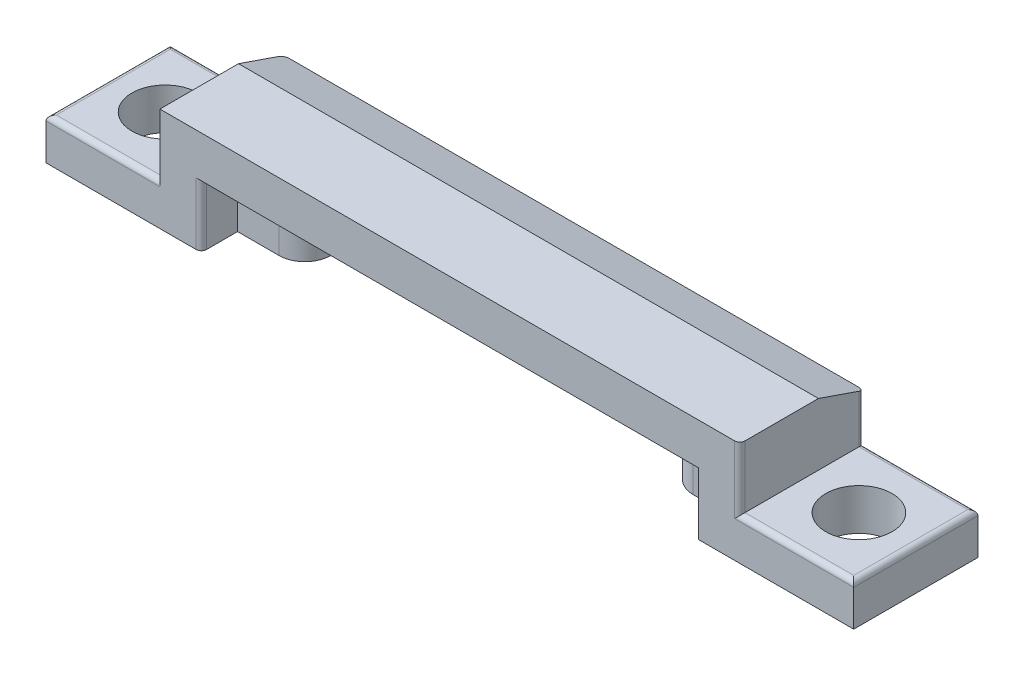
SolidWorks part; units mm, degrees
ref_plane "Ebene vorne" through (0, 0, 0) normal (0, 0, 1) x (1, 0, 0)
ref_plane "Ebene oben" through (0, 0, 0) normal (0, 1, 0) x (1, 0, 0)
ref_plane "Ebene rechts" through (0, 0, 0) normal (1, 0, 0) x (0, 0, -1)
sketch "Skizze1" plane through (0, 0, 0) normal (0, 0, 1) x (1, 0, 0)
  line L0 (0, 0) -> (7.5, 0)
  line L1 (7.5, 0) -> (7.5, 3)
  line L2 (7.5, 3) -> (31.5, 3)
  line L3 (31.5, 3) -> (31.5, 0)
  line L4 (31.5, 0) -> (39, 0)
  line L5 (39, 0) -> (39, 2)
  line L8 (33.5, 5) -> (5.5, 5)
  line L11 (0, 2) -> (0, 0)
  line L12 (33.5, 5) -> (33.5, 2)
  line L13 (-9, 2) -> (48, 2) construction
  line L14 (33.5, 2) -> (39, 2)
  line L15 (5.5, 5) -> (5.5, 2)
  line L16 (-9, 2) -> (48, 2) construction
  line L17 (5.5, 2) -> (0, 2)
  dimension "D1" = 24
  dimension "D2" = 3
  dimension "D3" = 7.5
  dimension "D4" = 7.5
  dimension "D5" = 5
  dimension "D9" = 2
  dimension "D10" = 2
extrude "Aufsatz-Linear austragen1" add sketch "Skizze1" along normal blind 6
sketch "Skizze4" plane through (0, 0, 0) normal (0, -1, 0) x (1, 0, 0)
  line L0 (39, 6) -> (39, 0) construction
  line L1 (31.5, 0) -> (39, 0) construction
  circle A0 centre (36.25, 3) radius 1.6
  dimension "D1" = 3.2
  dimension "D3" = 3
  dimension "D2" = 2.75
extrude "Schnitt-Linear austragen1" cut sketch "Skizze4" against normal blind 3
ref_plane "Ebene1" through (0, 5, 0) normal (0, -1, 0) x (-1, 0, 0)
ref_plane "Ebene2" through (19.5, 0, 0) normal (-1, 0, 0) x (0, 0, 1)
ref_plane "Ebene4" through (0, 0, 3) normal (0, 0, 1) x (1, 0, 0)
sketch "Skizze12" plane through (0, 3, 0) normal (0, -1, 0) x (1, 0, 0)
  line L0 (31.5, 1.75) -> (29.5, 1.75)
  line L1 (31.5, 6) -> (31.5, 0) construction
  line L2 (2.75, 3) -> (-2.75, 3) construction
  line L3 (29.5, 4.25) -> (31.5, 4.25)
  line L4 (31.5, 6) -> (31.5, 0) construction
  line L5 (31.5, 4.25) -> (31.5, 1.75)
  arc A0 (29.5, 1.75) -> (29.5, 4.25) centre (29.5, 3) cw
  dimension "D2" = 1.25
  dimension "D1" = 2
extrude "Aufsatz-Linear austragen2" add sketch "Skizze12" along normal blind 3
mirror "Spiegeln3" about plane through (19.5, 0, 0) normal (-1, 0, 0) of "Aufsatz-Linear austragen2"
mirror "Spiegeln4" about plane through (19.5, 0, 0) normal (-1, 0, 0) of "Schnitt-Linear austragen1"
fillet "Verrundung1" radius 0.25 10 edges at (7.5, 1.5, 6) (33.5, 3.5, 6) (33.5, 3.5, 0) (5.5, 3.5, 0) (2.75, 2, 6) (0, 2, 3) (2.75, 2, 0) (36.25, 2, 0) (39, 2, 3) (36.25, 2, 6)
sketch "Skizze13" plane through (33.5, 0, 0) normal (1, 0, 0) x (0, 0, -1)
  line L0 (-2.205, 5) -> (0, 4.24)
  line L1 (-5.75, 5) -> (-0.25, 5) construction
  line L2 (0, 5) -> (0, 1.75) construction
  line L3 (0, 4.24) -> (0, 5)
  line L4 (0, 5) -> (-2.205, 5)
  dimension "D1" = 2.205
  dimension "D2" = 0.76
extrude "Schnitt-Linear austragen2" cut sketch "Skizze13" against normal blind 30
